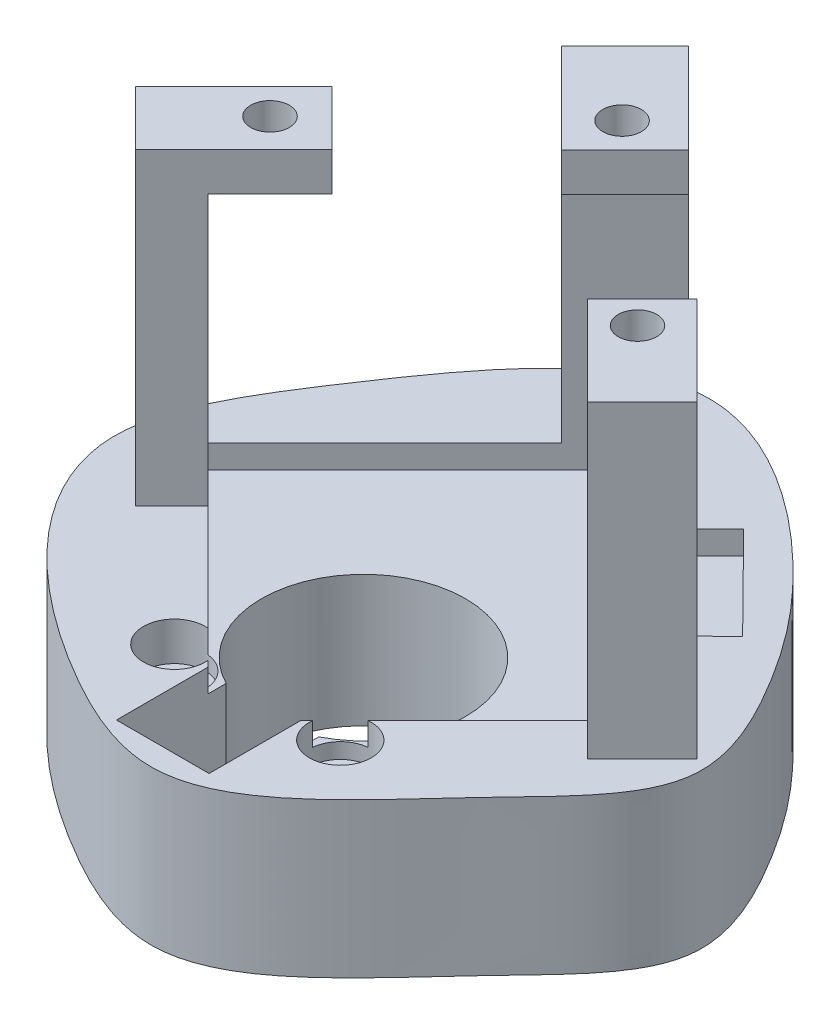
SolidWorks part; units mm, degrees
ref_plane "Front Plane" through (0, 0, 0) normal (0, 0, 1) x (1, 0, 0)
ref_plane "Top Plane" through (0, 0, 0) normal (0, 1, 0) x (1, 0, 0)
ref_plane "Right Plane" through (0, 0, 0) normal (1, 0, 0) x (0, 0, -1)
sketch "Sketch2" plane through (0, 0, 0) normal (0, 1, 0) x (1, 0, 0)
  circle A0 centre (0, 0) radius 60
extrude "Boss-Extrude1" add sketch "Sketch2" along normal blind 10 and the other way blind 10 contours A0
sketch "Sketch4" plane through (0, 10, 0) normal (0, 1, 0) x (1, 0, 0)
  circle A1 centre (0, 6) radius 13.225
sketch "Sketch6" plane through (0, 10, 0) normal (0, 1, 0) x (1, 0, 0)
  line L0 (-5.9779, 23.0428) -> (5.9779, 10.9572)
  line L1 (-5.9779, 23.0428) -> (13.2168, 42.0313)
  line L2 (5.9779, 10.9572) -> (25.1725, 29.9458)
  line L3 (13.2168, 42.0313) -> (25.1725, 29.9458)
  point P2 (15.5752, 20.4515)
  point P5 (3.6195, 32.537)
  dimension "D1" = 17
  dimension "D2" = 27
sketch "Sketch7" plane through (0, 10, 0) normal (0, 1, 0) x (1, 0, 0)
  circle A0 centre (-10.75, -7.75) radius 4
  dimension "D1" = 8
extrude "Cut-Extrude2" cut sketch "Sketch7" against normal blind 5 contours A0
mirror "Mirror1" about plane through (0, 0, 0) normal (1, 0, 0) of "Cut-Extrude2"
sketch "Sketch9" plane through (0, 10, 0) normal (0, 1, 0) x (1, 0, 0)
  line L0 (-31.1127, 17) -> (0, 48.1127)
  line L1 (-31.1127, 17) -> (0, -14.1127)
  line L2 (0, 48.1127) -> (31.1127, 17)
  line L3 (0, -14.1127) -> (31.1127, 17)
  dimension "D1" = 44
  dimension "D2" = 44
extrude "Cut-Extrude4" cut sketch "Sketch9" against normal blind 3
extrude "Cut-Extrude5" cut sketch "Sketch6" against normal blind 3
sketch "Sketch11" plane through (0, 10, 0) normal (0, 1, 0) x (1, 0, 0)
  line L0 (0, 48.1127) -> (-8.24, 39.8727)
  line L1 (0, 48.1127) -> (-4.5593, 52.672)
  line L2 (-8.24, 39.8727) -> (-12.7993, 44.432)
  line L3 (-4.5593, 52.672) -> (-12.7993, 44.432)
  line L4 (-31.1127, 17) -> (-24.0416, 9.9289)
  line L5 (-31.1127, 17) -> (-35.8263, 12.2864)
  line L6 (-24.0416, 9.9289) -> (-28.7552, 5.2154)
  line L7 (-35.8263, 12.2864) -> (-28.7552, 5.2154)
  line L8 (-31.1127, 17) -> (-10.3418, -3.7709) construction
  line L9 (31.6446, 17.5319) -> (24.5735, 10.4608)
  line L10 (31.6446, 17.5319) -> (35.9355, 13.241)
  line L11 (24.5735, 10.4608) -> (28.8645, 6.1699)
  line L12 (35.9355, 13.241) -> (28.8645, 6.1699)
  line L13 (10.3418, -3.7709) -> (31.1127, 17) construction
  line L14 (0, 48.1127) -> (-31.1127, 17) construction
  dimension "D1" = 11.6531
  dimension "D2" = 10
  dimension "D3" = 10
extrude "Boss-Extrude2" add sketch "Sketch11" along normal blind 35
sketch "Sketch12" plane through (0, 45, 0) normal (0, 1, 0) x (1, 0, 0)
  line L0 (-4.5593, 52.672) -> (-12.7993, 44.432)
  line L1 (-4.5593, 52.672) -> (7.108, 41.0047)
  line L2 (-12.7993, 44.432) -> (-1.132, 32.7647)
  line L3 (7.108, 41.0047) -> (-1.132, 32.7647)
  line L4 (-35.8263, 12.2864) -> (-28.7552, 5.2154)
  line L5 (-35.8263, 12.2864) -> (-23.0984, 25.0143)
  line L6 (-28.7552, 5.2154) -> (-16.0273, 17.9433)
  line L7 (-23.0984, 25.0143) -> (-16.0273, 17.9433)
  line L8 (35.9355, 13.241) -> (28.8645, 6.1699)
  line L9 (35.9355, 13.241) -> (24.3378, 24.8387)
  line L10 (28.8645, 6.1699) -> (17.2667, 17.7677)
  line L11 (24.3378, 24.8387) -> (17.2667, 17.7677)
extrude "Boss-Extrude3" add sketch "Sketch12" along normal blind 5
sketch "Sketch13" plane through (0, 50, 0) normal (0, 1, 0) x (1, 0, 0)
  circle A0 centre (-0.5, 40) radius 2.5
  dimension "D1" = 5
sketch "Sketch14" plane through (0, 50, 0) normal (0, 1, 0) x (1, 0, 0)
  circle A0 centre (23.5, 18) radius 2.5
sketch "Sketch15" plane through (0, 50, 0) normal (0, 1, 0) x (1, 0, 0)
  circle A0 centre (-23.777, 17.669) radius 2.5
extrude "Cut-Extrude7" cut sketch "Sketch13" against normal blind 5 contours A0
extrude "Cut-Extrude8" cut sketch "Sketch15" against normal blind 5 contours A0
extrude "Cut-Extrude9" cut sketch "Sketch14" against normal blind 5 contours A0
sketch "Sketch16" plane through (0, 10, 0) normal (0, 1, 0) x (1, 0, 0)
  spline S0 degree 3 poles (-27.5345, 35.3123) (-7.4919, 63.2621) (20.1768, 43.1639) (32.0959, 27.7397) (41.1035, 9.3847) (23.4414, -7.0123) (7.3872, -27.6695) (-20.6756, -15.2656) (-45.2159, 6.8631) (-27.5345, 35.3123) (-7.4919, 63.2621) (20.1768, 43.1639) knots -0.41993 -0.246246 -0.147029 0 0.129983 0.21607 0.283536 0.368924 0.507401 0.58007 0.753754 0.852971 1 1.129983 1.21607 1.283536 only from (-4.7945, 54.4115) to (-4.7945, 54.4115)
  circle M1 centre (0, 0) radius 60
extrude "Cut-Extrude10" cut sketch "Sketch16" against normal blind 38 contours S0 M1 | S0 region at (-58.3029, 10, 0)
extrude "Cut-Extrude12" cut sketch "Sketch4" against normal blind 42 contours A1
sketch "Sketch19" plane through (0, 10, 0) normal (0, 1, 0) x (1, 0, 0)
  line L0 (-6, 0) -> (-6, -20)
  line L1 (-6, 0) -> (6, 0)
  line L2 (-6, -20) -> (6, -20)
  line L3 (6, 0) -> (6, -20)
extrude "Cut-Extrude13" cut sketch "Sketch19" against normal blind 17
